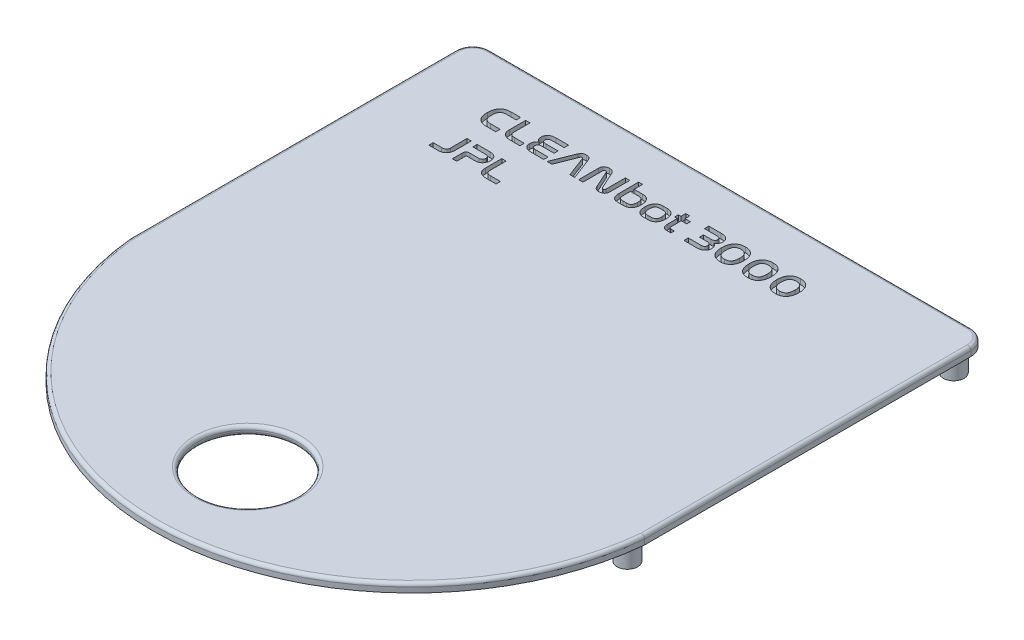
SolidWorks part; units mm, degrees
material "6063-O"
ref_plane "Front Plane" through (0, 0, 0) normal (0, 0, 1) x (1, 0, 0)
ref_plane "Top Plane" through (0, 0, 0) normal (0, 1, 0) x (1, 0, 0)
ref_plane "Right Plane" through (0, 0, 0) normal (1, 0, 0) x (0, 0, -1)
sketch "Sketch1" plane through (0, 0, 0) normal (0, 1, 0) x (1, 0, 0)
  line L1 (-190.5, -213.36) -> (190.5, -213.36)
  line L2 (-190.5, -213.36) -> (-190.5, 213.36)
  line L3 (-190.5, 213.36) -> (190.5, 213.36)
  line L4 (190.5, -213.36) -> (190.5, 213.36)
  line L5 (-190.5, -213.36) -> (190.5, 213.36) construction
  line L6 (-190.5, 213.36) -> (190.5, -213.36) construction
  arc A0 (190.5, -40.64) -> (-190.5, -40.64) centre (0, -21.9449) cw
  point P0 (0, 0)
  dimension "D1" = 381
  dimension "D2" = 426.72
  dimension "D3" = 254
extrude "Boss-Extrude1" add sketch "Sketch1" along normal blind 6.35 contours L4 L3 L2 L1 region at (0, 0, -17.9529)
fillet "Fillet1" radius 12.7 2 edges at (190.5, 3.175, -213.36) (-190.5, 3.175, -213.36)
sketch "Sketch5" plane through (0, 0, 0) normal (0, -1, 0) x (1, 0, 0)
  line L0 (-177.8, 40.64) -> (-177.8, -200.66) construction
  circle A0 centre (-177.8, 40.64) radius 7.62
  circle A1 centre (-177.8, -200.66) radius 7.62
  circle A2 centre (-177.8, 40.64) radius 3.175
  circle A3 centre (-177.8, -200.66) radius 3.175
  arc A4 (-190.5, -200.66) -> (-177.8, -213.36) centre (-177.8, -200.66) ccw construction
  dimension "D1" = 15.24
  dimension "D2" = 6.35
extrude "Boss-Extrude4" add sketch "Sketch5" along normal blind 16.51
mirror "Mirror1" about plane through (0, 0, 0) normal (1, 0, 0) of "Boss-Extrude4"
sketch "Sketch6" plane through (0, 6.35, 0) normal (0, 1, 0) x (1, 0, 0)
  circle A0 centre (0, -143.51) radius 36.83
  arc A1 (-190.5, -40.64) -> (190.5, -40.64) centre (0, -21.9449) ccw construction
  point P8 (0, -213.36)
  dimension "D1" = 73.66
  dimension "D2" = 69.85
extrude "Cut-Extrude1" cut sketch "Sketch6" against normal up to surface (6.35 mm away) up to face at (177.8, 0, 33.02)
sketch "Sketch7" plane through (0, 6.35, 0) normal (0, 1, 0) x (1, 0, 0)
  line L0 (-190.5, -40.64) -> (-190.5, 200.66) construction
  line L2 (-177.8, 213.36) -> (177.8, 213.36) construction
  text T0 "CLEANbot 3000\r\nJPL\r\n" font "Nasalization Rg" height in points 72
  dimension "D1" = 50.8
  dimension "D2" = 50.8
extrude "Cut-Extrude2" cut sketch "Sketch7" against normal blind 3.81
fillet "Fillet2" radius 2.54 8 edges at (0, 6.35, 180.34) (0, 0, 180.34) (-190.5, 6.35, -80.01) (-186.7803, 6.35, -209.6403) (0, 6.35, -213.36) (186.7803, 6.35, -209.6403) (190.5, 6.35, -80.01) (0, 6.35, 213.36)
